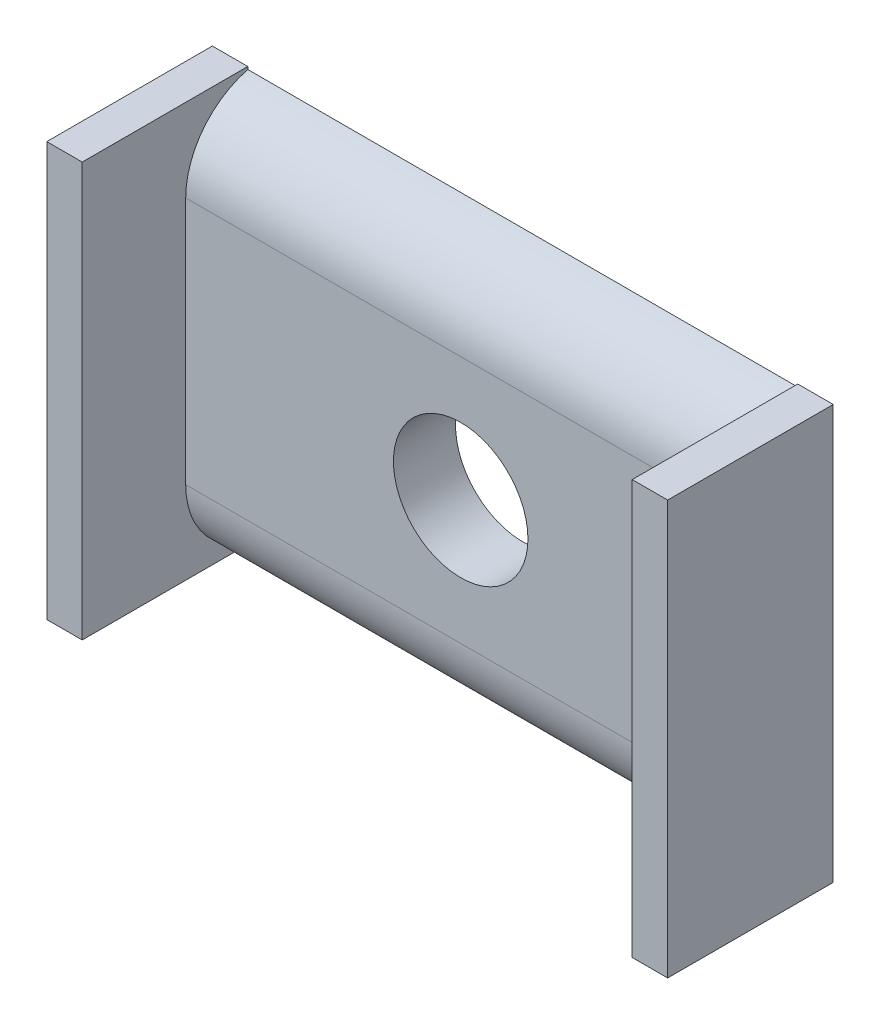
SolidWorks part; units mm, degrees
ref_plane "Alzado" through (0, 0, 0) normal (0, 0, 1) x (1, 0, 0)
ref_plane "Planta" through (0, 0, 0) normal (0, 1, 0) x (1, 0, 0)
ref_plane "Vista lateral" through (0, 0, 0) normal (1, 0, 0) x (0, 0, -1)
sketch "Croquis1" plane through (0, 0, 0) normal (0, 0, 1) x (1, 0, 0)
  line L1 (-15, -10) -> (15, -10)
  line L2 (-15, -10) -> (-15, 10)
  line L3 (-15, 10) -> (15, 10)
  line L4 (15, -10) -> (15, 10)
  line L5 (-15, -10) -> (15, 10) construction
  line L6 (-15, 10) -> (15, -10) construction
  circle A0 centre (0, 0) radius 3.25
  point P0 (0, 0)
  dimension "D3" = 6.5
  dimension "D1" = 30
  dimension "D2" = 20
extrude "Saliente-Extruir1" add sketch "Croquis1" along normal blind 3
sketch "Croquis3" plane through (0, 0, 3) normal (0, 0, 1) x (1, 0, 0)
  line L0 (-15, -10) -> (15, -10) construction
  line L1 (-15, 10) -> (-13.2871, 10)
  line L2 (-15, 10) -> (-15, -10)
  line L3 (-15, -10) -> (-13.2871, -10)
  line L4 (-13.2871, 10) -> (-13.2871, -10)
  line L5 (0, 0) -> (0, 2.8288) construction
  line L6 (15, -10) -> (13.2871, -10)
  line L7 (13.2871, 10) -> (13.2871, -10)
  line L8 (15, 10) -> (13.2871, 10)
  line L9 (15, 10) -> (15, -10)
extrude "Saliente-Extruir2" add sketch "Croquis3" along normal blind 5
fillet "Redondeo1" radius 4 1 edges at (0, 10, 3)
fillet "Redondeo2" radius 4 1 edges at (0, -10, 3)
